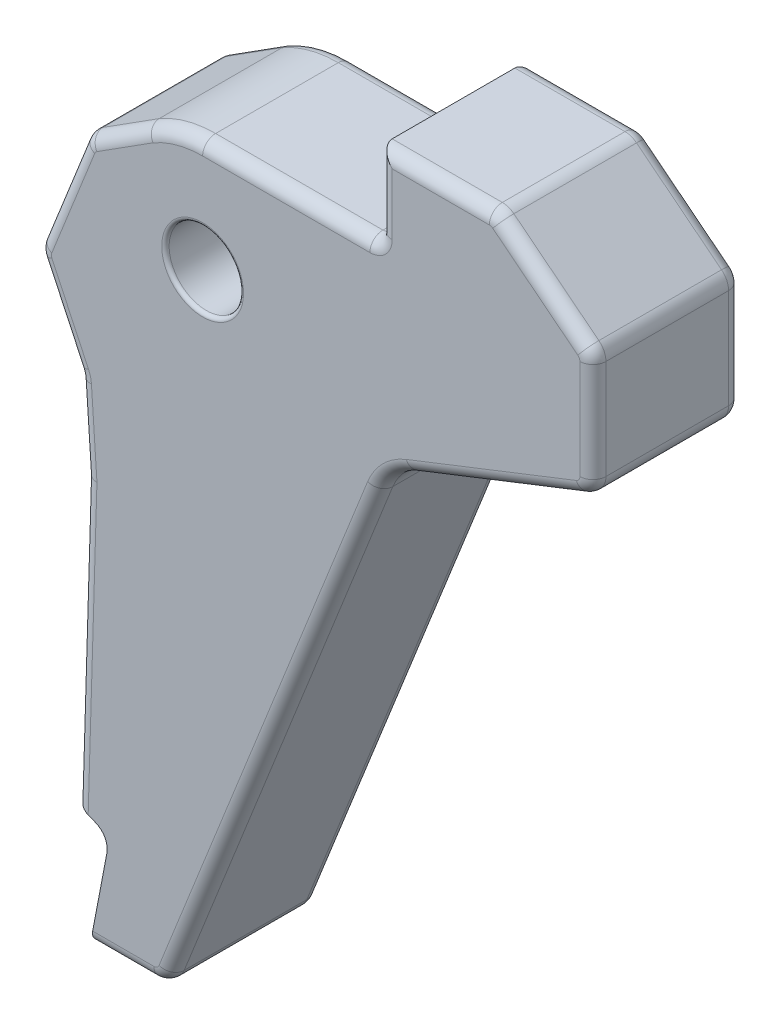
SolidWorks part; units mm, degrees
ref_plane "정면" through (0, 0, 0) normal (0, 0, 1) x (1, 0, 0)
ref_plane "윗면" through (0, 0, 0) normal (0, 1, 0) x (1, 0, 0)
ref_plane "우측면" through (0, 0, 0) normal (1, 0, 0) x (0, 0, -1)
sketch "스케치1" plane through (0, 0, 0) normal (0, 0, 1) x (1, 0, 0)
  line L0 (0, 6) -> (9, 6)
  line L1 (9.5, 6.5) -> (9.5, 10.5)
  line L2 (9.5, 10.5) -> (15.4256, 10.5)
  line L3 (16.0465, 10.2839) -> (20.6209, 6.6602)
  line L4 (21, 5.8763) -> (21, 0.5149)
  line L5 (20.3657, -0.4159) -> (11.2201, -4.009)
  line L6 (9.5304, -5.6902) -> (-1.6932, -33.8436)
  line L7 (-2.6221, -34.4733) -> (-6.0491, -34.4733)
  line L8 (-6.0491, -34.4733) -> (-5.1512, -29.756)
  line L9 (-5.7632, -28.6401) -> (-6.8512, -28.2063)
  line L10 (-6.8512, -28.2063) -> (-6.3865, -12.759)
  line L11 (-6.3865, -12.759) -> (-6.6804, -8.3621)
  line L12 (-6.7733, -8.0031) -> (-8.7428, -3.8166)
  line L13 (-8.7669, -3.0206) -> (-6.4556, 2.7771)
  line L14 (-6.0632, 3.2506) -> (-3.036, 5.1752)
  circle A0 centre (0, 0) radius 2
  arc A1 (0, 6) -> (-3.3981, 4.945) centre (0, 0) ccw
  arc A2 (-6.6804, -8.3621) -> (-6.7733, -8.0031) centre (-7.6782, -8.4288) ccw
  arc A3 (-6.4556, 2.7771) -> (-6.0632, 3.2506) centre (-5.5267, 2.4068) cw
  arc A4 (15.4256, 10.5) -> (16.0465, 10.2839) centre (15.4256, 9.5) cw
  arc A5 (20.6209, 6.6602) -> (21, 5.8763) centre (20, 5.8763) cw
  arc A6 (21, 0.5149) -> (20.3657, -0.4159) centre (20, 0.5149) cw
  arc A7 (-1.6932, -33.8436) -> (-2.6221, -34.4733) centre (-2.6221, -33.4733) cw
  arc A8 (-5.1512, -29.756) -> (-5.7632, -28.6401) centre (-6.1335, -29.569) ccw
  arc A9 (-8.7428, -3.8166) -> (-8.7669, -3.0206) centre (-7.838, -3.3909) cw
  arc A10 (11.2201, -4.009) -> (9.5304, -5.6902) centre (12.3172, -6.8012) ccw
  arc A11 (9, 6) -> (9.5, 6.5) centre (9, 6.5) ccw
  dimension "D1" = 4
  dimension "D2" = 12
  dimension "D6" = 1
  dimension "D7" = 3
  dimension "D8" = 0.5
  dimension "D3" = 35
  dimension "D4" = 21
  dimension "D5" = 10.5
  dimension "D9" = 9
extrude "보스-돌출1" add sketch "스케치1" along normal blind 8 contours A11 L0 A1 L14 A3 L13 A9 L12 A2 L11 L10 L9 A8 L8 L7 A7 L6 A10 L5 A6 L4 A5 L3 A4 L2 L1 A0 region at (3.2823, -7.5043, 0)
fillet "필렛2" radius 0.7 46 edges at (-1.573, 5.7901, 0) (9.5, 8.5, 0) (9.3536, 6.1464, 0) (-1.573, 5.7901, 8) (9.5, 8.5, 8) (9.3536, 6.1464, 8) (-4.5496, 4.2129, 0) (-6.2967, 3.0448, 0) (-7.6112, -0.1218, 0) (-8.8375, -3.4211, 0) (-7.7581, -5.9098, 0) (-6.7101, -8.1782, 0) (-4.5496, 4.2129, 8) (-6.2967, 3.0448, 8) (-7.6112, -0.1218, 8) (-8.8375, -3.4211, 8) (-7.7581, -5.9098, 8) (-6.7101, -8.1782, 8) (12.4628, 10.5, 0) (15.7543, 10.4444, 0) (18.3337, 8.472, 0) (20.9003, 6.3116, 0) (21, 3.1956, 0) (20.8263, -0.0483, 0) (15.7929, -2.2124, 0) (10.2011, -4.6746, 0) (-4.3356, -34.4733, 0) (-2.061, -34.301, 0) (12.4628, 10.5, 8) (15.7543, 10.4444, 8) (18.3337, 8.472, 8) (20.9003, 6.3116, 8) (21, 3.1956, 8) (20.8263, -0.0483, 8) (15.7929, -2.2124, 8) (10.2011, -4.6746, 8) (-4.3356, -34.4733, 8) (-2.061, -34.301, 8) (4.5, 6, 0) (4.5, 6, 8) (-6.5335, -10.5606, 0) (-6.5335, -10.5606, 8) (-6.6189, -20.4827, 0) (-6.6189, -20.4827, 8) (3.9186, -19.7669, 0) (3.9186, -19.7669, 8)
fillet "필렛3" radius 0.2 2 edges at (2, 0, 0) (2, 0, 8)
